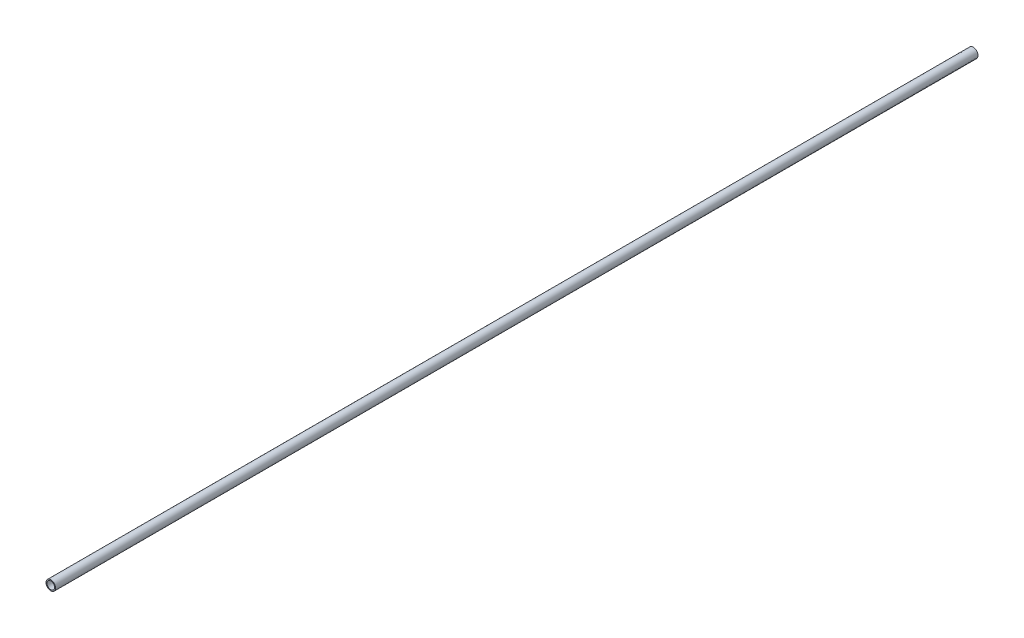
SolidWorks part; units mm, degrees
material "Hexcel AS4C (3000 Filaments)"
ref_plane "Front Plane" through (0, 0, 0) normal (0, 0, 1) x (1, 0, 0)
ref_plane "Top Plane" through (0, 0, 0) normal (0, 1, 0) x (1, 0, 0)
ref_plane "Right Plane" through (0, 0, 0) normal (1, 0, 0) x (0, 0, -1)
sketch "Sketch1" plane through (0, 0, 0) normal (0, 0, 1) x (1, 0, 0)
  circle A0 centre (0, 0) radius 6.35
  circle A1 centre (0, 0) radius 5.08
  dimension "D1" = 12.7
  dimension "D2" = 10.16
extrude "Boss-Extrude1" add sketch "Sketch1" along normal blind 1219.2
sketch "Sketch2" plane through (0, 0, 1219.2) normal (0, 0, 1) x (1, 0, 0)
  circle A0 centre (0, 0) radius 6.35 construction
  point P0 (0, -6.35)
ref_plane "LeftSupport" through (0, 0, 1206.5) normal (0, 0, 1) x (1, 0, 0)
ref_plane "RightSuppor" through (0, 0, 12.7) normal (0, 0, -1) x (-1, 0, 0)
ref_plane "Plane3" through (0, 6.35, 0) normal (0, 1, 0) x (1, 0, 0)
sketch "Roller1" plane through (0, 6.35, 0) normal (0, 1, 0) x (1, 0, 0)
  circle A0 centre (0, -12.7) radius 3.175
  dimension "D1" = 6.35
  dimension "D2" = 12.7
sketch "Roller2" plane through (0, 6.35, 0) normal (0, 1, 0) x (1, 0, 0)
  line L0 (-6.35, -1219.2) -> (6.35, -1219.2) construction
  circle A0 centre (0, -1206.5) radius 3.175
  dimension "D1" = 6.35
  dimension "D2" = 12.7
